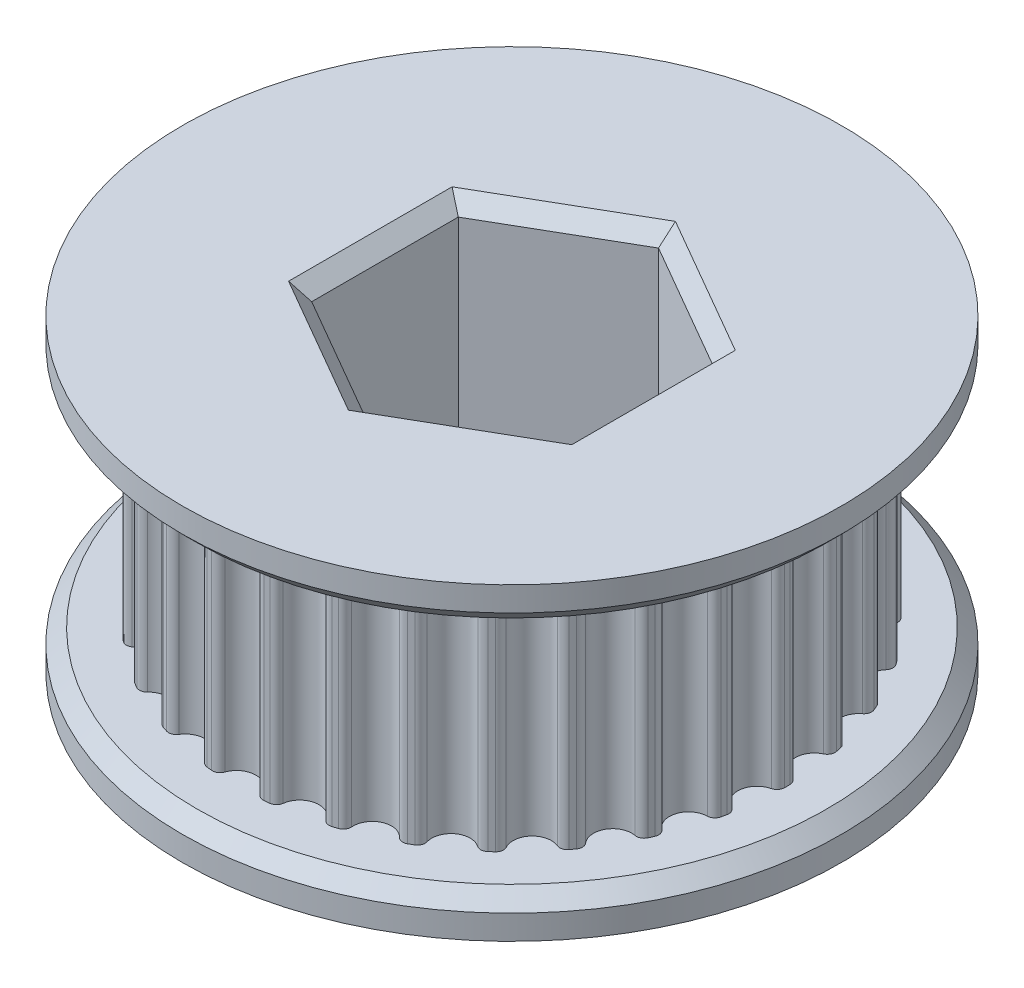
SolidWorks part; units mm, degrees
ref_plane "Front Plane" through (0, 0, 0) normal (0, 0, 1) x (1, 0, 0)
ref_plane "Top Plane" through (0, 0, 0) normal (0, 1, 0) x (1, 0, 0)
ref_plane "Right Plane" through (0, 0, 0) normal (1, 0, 0) x (0, 0, -1)
sketch "Sketch1" plane through (0, 0, 0) normal (0, 1, 0) x (1, 0, 0)
  circle A0 centre (0, 0) radius 14.3239
  circle A1 centre (0, 14.3239) radius 1
  dimension "D1" = 28.6479
  dimension "D2" = 2
extrude "Boss-Extrude2" add sketch "Sketch1" along normal blind 12 contours A1 A0 | A0 A1 region at (0, 0, 0.0334) region at (0, 0, -13.8933)
extrude "Cut-Extrude3" cut sketch "Sketch1<3>" against normal through all and the other way through all contours A1
sketch "Sketch1<3>" plane through (0, 0, 0) normal (0, 1, 0) x (1, 0, 0) same geometry as "Sketch1"
fillet "Fillet1" radius 0.4 2 edges at (-0.9994, 6, -14.289) (0.9994, 6, -14.289)
pattern_circular "CirPattern2" count 30 over 360 about axis through (0, 12, 0) along (0, 1, 0) of "Fillet1", "Cut-Extrude3"
sketch "Sketch2" plane through (0, 12, 0) normal (0, 1, 0) x (1, 0, 0)
  line L1 (-6.604, -3.8128) -> (0, -7.6256)
  line L2 (0, -7.6256) -> (6.604, -3.8128)
  line L3 (6.604, -3.8128) -> (6.604, 3.8128)
  line L4 (6.604, 3.8128) -> (0, 7.6256)
  line L5 (0, 7.6256) -> (-6.604, 3.8128)
  line L6 (-6.604, 3.8128) -> (-6.604, -3.8128)
  circle A1 centre (0, 0) radius 17.145
  circle A2 centre (0, 0) radius 6.604 construction
  dimension "D1" = 13.208
  dimension "D2" = 34.29
extrude "Boss-Extrude3" add sketch "Sketch2" along normal blind 2.032
extrude "Boss-Extrude4" add sketch "Sketch2<2>" against normal blind 2.032 from surface starting at face at (0, 0, 0)
sketch "Sketch2<2>" plane through (0, 12, 0) normal (0, 1, 0) x (1, 0, 0) same geometry as "Sketch2"
extrude "Cut-Extrude4" cut sketch "Sketch2<3>" against normal through all contours L5 L6 L1 L2 L3 L4 region at (0, 12, 0)
sketch "Sketch2<3>" plane through (0, 12, 0) normal (0, 1, 0) x (1, 0, 0) same geometry as "Sketch2"
chamfer "Chamfer1" distance 0.762 angle 45 12 edges at (-3.302, -2.032, -5.7192) (3.302, -2.032, -5.7192) (6.604, -2.032, 0) (-6.604, -2.032, 0) (-3.302, -2.032, 5.7192) (3.302, -2.032, 5.7192) (6.604, 14.032, 0) (3.302, 14.032, 5.7192) (-3.302, 14.032, 5.7192) (-6.604, 14.032, 0) (3.302, 14.032, -5.7192) (-3.302, 14.032, -5.7192)
chamfer "Chamfer2" distance 0.762 angle 45 2 edges at (0, 12, 17.145) (0, 0, 17.145)
equation "\"teeth\"= 30"
equation "\"D1@Sketch1\"=(\"teeth\" * 3) / (pi * 25.4)"
